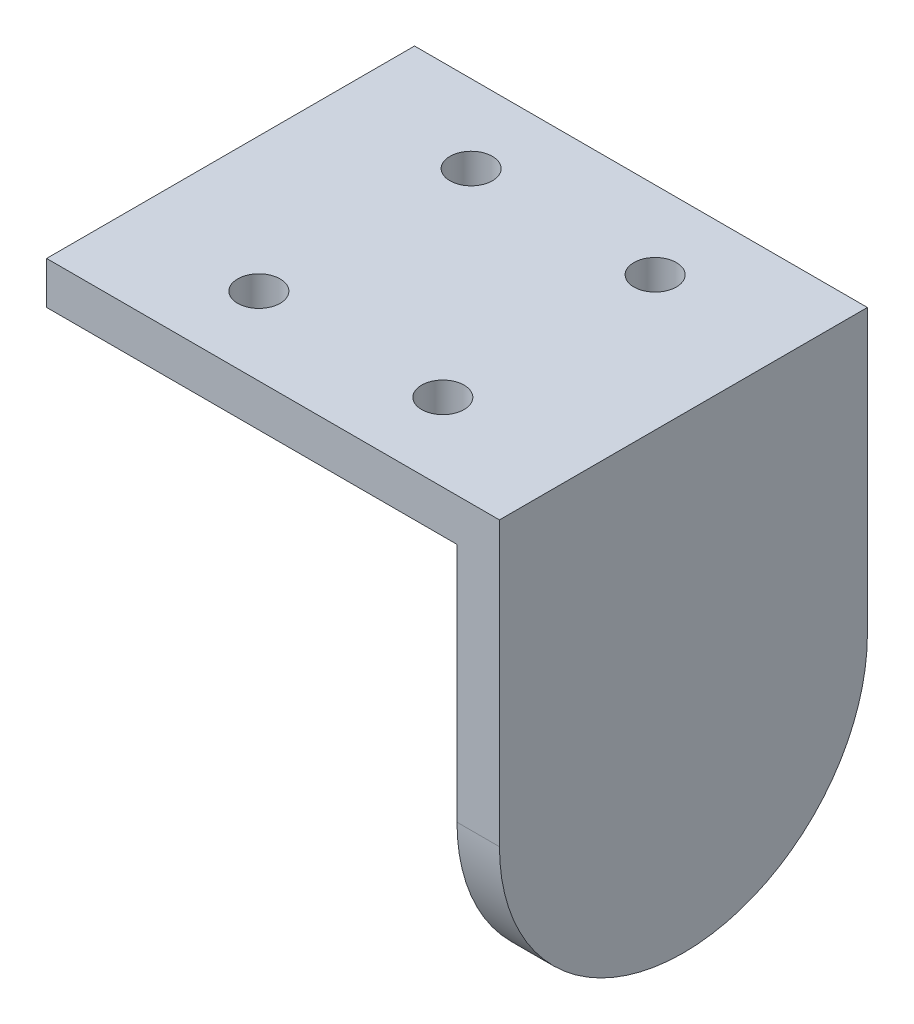
SolidWorks part; units mm, degrees
ref_plane "Front Plane" through (0, 0, 0) normal (0, 0, 1) x (1, 0, 0)
ref_plane "Top Plane" through (0, 0, 0) normal (0, 1, 0) x (1, 0, 0)
ref_plane "Right Plane" through (0, 0, 0) normal (1, 0, 0) x (0, 0, -1)
sketch "Sketch1" plane through (0, 0, 0) normal (0, 0, 1) x (1, 0, 0)
  line L0 (0, 0) -> (3, 0)
  line L1 (3, 0) -> (3, 33)
  line L2 (3, 33) -> (-29, 33)
  line L3 (-29, 33) -> (-29, 30)
  line L4 (-29, 30) -> (0, 30)
  line L5 (0, 30) -> (0, 0)
  dimension "D1" = 3
  dimension "D2" = 3
  dimension "D3" = 30
  dimension "D4" = 29
extrude "Boss-Extrude1" add sketch "Sketch1" along normal blind 26
fillet "Fillet1" radius 13 2 edges at (1.5, 0, 0) (1.5, 0, 26)
sketch "Sketch2" plane through (0, 33, 0) normal (0, 1, 0) x (1, 0, 0)
  line L0 (-19.5, -7) -> (-19.5, -19) construction
  line L1 (-18, -5.5) -> (-8, -5.5) construction
  line L2 (-6.5, -7) -> (-6.5, -19) construction
  line L3 (-18, -20.5) -> (-8, -20.5) construction
  line L4 (-29, 0) -> (-29, -26) construction
  line L5 (-29, 0) -> (3, 0) construction
  circle A0 centre (-19.5, -5.5) radius 1.5
  circle A2 centre (-19.5, -20.5) radius 1.5
  circle A3 centre (-6.5, -5.5) radius 1.5
  circle A4 centre (-6.5, -20.5) radius 1.5
  point P16 (-13, 0)
  point P20 (-13, -5.5)
  point P21 (-29, -13)
  point P25 (-19.5, -13)
  dimension "D1" = 3
  dimension "D2" = 12
  dimension "D3" = 10
extrude "Cut-Extrude1" cut sketch "Sketch2" against normal up to next
